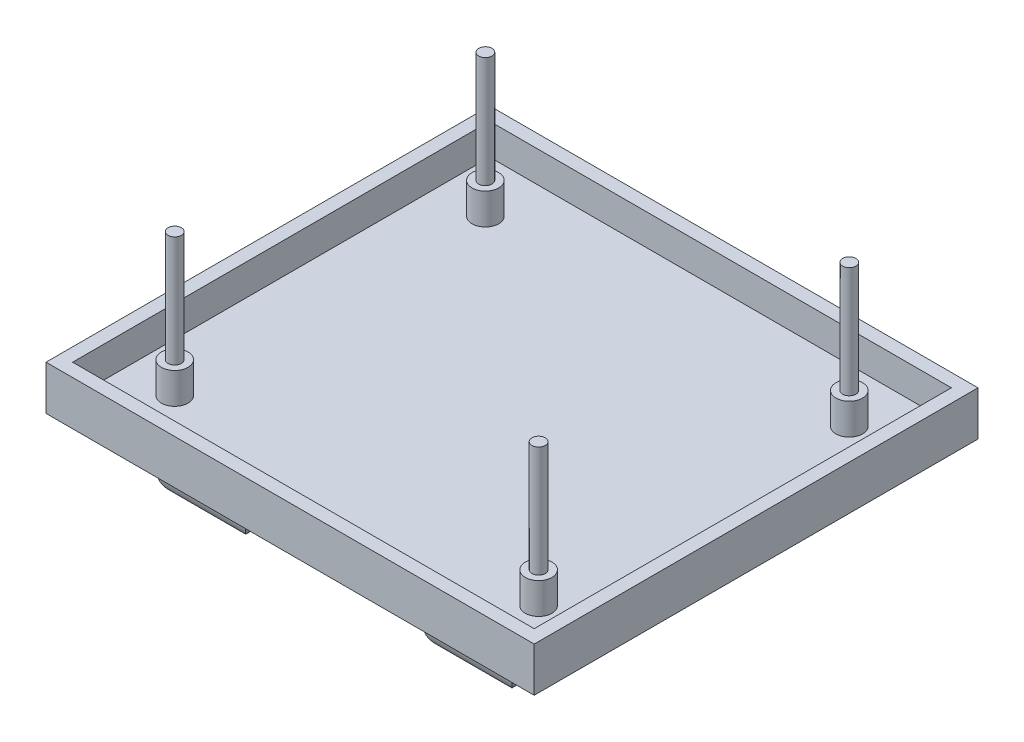
SolidWorks part; units mm, degrees
ref_plane "Front Plane" through (0, 0, 0) normal (0, 0, 1) x (1, 0, 0)
ref_plane "Top Plane" through (0, 0, 0) normal (0, 1, 0) x (1, 0, 0)
ref_plane "Right Plane" through (0, 0, 0) normal (1, 0, 0) x (0, 0, -1)
sketch "Sketch1" plane through (0, 0, 0) normal (0, 1, 0) x (1, 0, 0)
  line L1 (-55, 50) -> (55, 50)
  line L2 (-55, 50) -> (-55, -50)
  line L3 (-55, -50) -> (55, -50)
  line L4 (55, 50) -> (55, -50)
  line L5 (-55, 50) -> (55, -50) construction
  line L6 (-55, -50) -> (55, 50) construction
  point P0 (0, 0)
  dimension "D1" = 100
  dimension "D2" = 110
extrude "Boss-Extrude1" add sketch "Sketch1" along normal blind 3
sketch "Sketch2" plane through (0, 3, 0) normal (0, 1, 0) x (1, 0, 0)
  line L0 (55, 50) -> (-55, 50) construction
  line L1 (55, -50) -> (55, 50) construction
  line L2 (0, 53.225) -> (0, -57.2845) construction
  line L3 (-57.1342, 0) -> (61.4944, 0) construction
  line L5 (-55, 50) -> (-55, -50)
  line L6 (-55, -50) -> (55, -50)
  line L7 (55, -50) -> (55, 50)
  line L8 (55, 50) -> (-55, 50)
  line L9 (-52, 47) -> (52, 47)
  line L10 (-52, 47) -> (-52, -47)
  line L11 (-52, -47) -> (52, -47)
  line L12 (52, -47) -> (52, 47)
  circle A0 centre (41, 35) radius 3
  circle A1 centre (-41, 35) radius 3
  circle A2 centre (41, -35) radius 3
  circle A3 centre (-41, -35) radius 3
  line M6 (55, -50) -> (55, 50)
  line M7 (55, 50) -> (-55, 50)
  line M8 (-55, 50) -> (-55, -50)
  line M9 (-55, -50) -> (55, -50)
  dimension "D1" = 6
  dimension "D2" = 15
  dimension "D3" = 14
  dimension "D4" = 3
  dimension "D5" = 104
  dimension "D6" = 52
  dimension "D7" = 94
extrude "Boss-Extrude2" add sketch "Sketch2" along normal blind 7 contours L12 L11 L10 L9 M9 M6 M7 M8 | A1 | A3 | A0 | A2 region at (0, 3, -48.5134) region at (41, 3, -35) region at (-41, 3, -35) region at (-41, 3, 35)
sketch "Sketch3" plane through (0, 10, 0) normal (0, 1, 0) x (1, 0, 0)
  circle A0 centre (-41, 35) radius 1.5
  circle A1 centre (41, 35) radius 1.5
  circle A2 centre (41, -35) radius 1.5
  circle A3 centre (-41, -35) radius 1.5
extrude "Boss-Extrude3" add sketch "Sketch3" along normal blind 25
sketch "Sketch5" plane through (0, 0, 0) normal (0, -1, 0) x (1, 0, 0)
  line L0 (0, 44.0534) -> (0, -39.6932) construction
  line L1 (-40, 40) -> (-20, 40)
  line L2 (-20, -40) -> (-40, -40)
  line L3 (-20, -40) -> (-20, -32)
  line L4 (-20, 40) -> (-40, 40)
  line L5 (-40, -40) -> (-40, -32)
  line L6 (20, -32) -> (20, -40)
  line L7 (40, -32) -> (20, -32)
  line L8 (-20, 32) -> (-40, 32)
  line L9 (-40, 32) -> (-40, 40)
  line L10 (-40, -40) -> (-40, -32)
  line L11 (-40, -32) -> (-20, -32)
  line L12 (-20, -32) -> (-20, -40)
  line L13 (-40, 32) -> (-40, 40)
  line L14 (-20, 32) -> (-20, 40)
  line L15 (40, -40) -> (40, -32)
  line L16 (40, -40) -> (40, -32)
  line L17 (20, -40) -> (20, -32)
  line L18 (20, -40) -> (40, -40)
  line L19 (20, 32) -> (20, 40)
  line L20 (40, 32) -> (40, 40)
  line L21 (40, 32) -> (40, 40)
  line L22 (20, 32) -> (40, 32)
  line L23 (20, 40) -> (40, 40)
  line L24 (40, 40) -> (20, 40)
  point P3 (-30, 0)
  dimension "D1" = 30
  dimension "D2" = 20
  dimension "D3" = 80
  dimension "D4" = 8
  dimension "D5" = 8
extrude "Boss-Extrude4" add sketch "Sketch5" along normal blind 10 contours L11 L5 L2 L3 | L8 L14 L1 L9 | L23 L19 L22 L20 | L6 L18 L15 L7 region at (-30, 0, 36) region at (-30, 0, -36) region at (30, 0, -36) region at (30, 0, 36)
sketch "Sketch6" plane through (0, -10, 0) normal (0, -1, 0) x (1, 0, 0)
  line L0 (-40, 40) -> (-20, 40)
  line L1 (-20, 40) -> (-20, -40)
  line L2 (-20, -40) -> (-40, -40)
  line L3 (-40, -40) -> (-40, 40)
  line L4 (20, 40) -> (40, 40)
  line L5 (40, 40) -> (40, -40)
  line L6 (40, -40) -> (20, -40)
  line L7 (20, -40) -> (20, 40)
extrude "Boss-Extrude5" add sketch "Sketch6" along normal blind 4
fillet "Fillet1" radius 5 8 edges at (-40, -14, 0) (-20, -14, 0) (20, -14, 0) (40, -14, 0) (30, -14, 40) (-30, -14, 40) (30, -14, -40) (-30, -14, -40)
